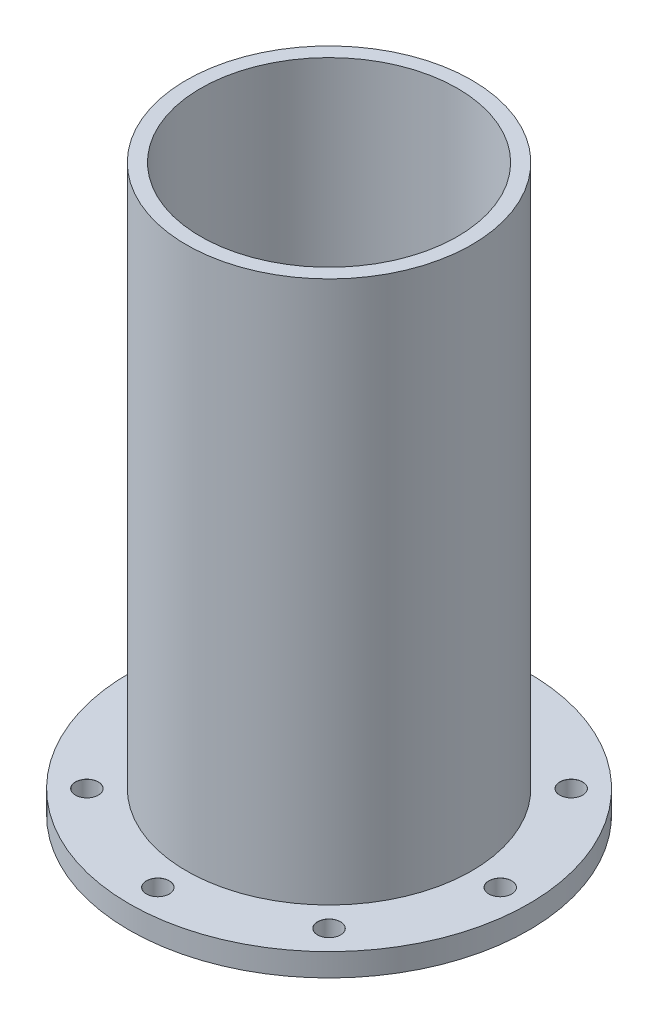
SolidWorks part; units mm, degrees
ref_plane "Front Plane" through (0, 0, 0) normal (0, 0, 1) x (1, 0, 0)
ref_plane "Top Plane" through (0, 0, 0) normal (0, 1, 0) x (1, 0, 0)
ref_plane "Right Plane" through (0, 0, 0) normal (1, 0, 0) x (0, 0, -1)
sketch "草图1" plane through (0, 0, 0) normal (0, 0, 1) x (1, 0, 0)
  line L0 (0, 76.6195) -> (0, -49.9786) construction
  line L13 (0, 0) -> (-70, 0)
  line L14 (0, 0) -> (0, 8)
  line L15 (0, 8) -> (-70, 8)
  line L16 (-70, 0) -> (-70, 8)
  dimension "D1" = 70
  dimension "D2" = 8
revolve "旋转1" add sketch "草图1" angle 360 about L0
sketch "草图8" plane through (0, 8, 0) normal (0, 1, 0) x (1, 0, 0)
  circle A0 centre (0, 0) radius 60
  dimension "D1" = 120
hole_wizard "M8x1.0 螺纹孔2" positions "草图9" profile "草图10" tap size "M8x1.0" standard "GB" end condition through all
sketch "草图9" plane through (0, 8, 0) normal (0, 1, 0) x (1, 0, 0)
  circle A0 centre (0, 0) radius 60 construction
  point P0 (-60, 0)
sketch "草图10" plane through (-60, 8, 0) normal (1, 0, 0) x (0, 0, 1)
  line L0 (0, 0) -> (0, 8)
  line L1 (0, 8) -> (4, 8)
  line L2 (4, 8) -> (4, 0.021)
  line L3 (4, 0.021) -> (4.025, 0)
  line L5 (4.025, 0) -> (0, 0)
  line L6 (-4, 0.021) -> (-4.025, 0) construction
  line L11 (0, -6.35) -> (0, 107.95) construction
  dimension "通孔螺纹孔钻头直径" = 8
  dimension "通孔螺纹孔钻头深度" = 8
  dimension "近端锥形沉头孔直径" = 8.05
  dimension "近端锥形沉头孔角度" = 100
cosmetic thread "孔螺蚊线9" parameters "D2"=8
pattern_circular "阵列(圆周)2" count 8 over 360 about axis through (0, 76.6195, 0) along (0, -1, 0) of "M8x1.0 螺纹孔2"
cosmetic thread "孔螺蚊线10" parameters "D2"=8
cosmetic thread "孔螺蚊线11" parameters "D2"=8
cosmetic thread "孔螺蚊线12" parameters "D2"=8
cosmetic thread "孔螺蚊线13" parameters "D2"=8
cosmetic thread "孔螺蚊线14" parameters "D2"=8
cosmetic thread "孔螺蚊线15" parameters "D2"=8
cosmetic thread "孔螺蚊线16" parameters "D2"=8
sketch "草图11" plane through (0, 0, 0) normal (0, 0, 1) x (1, 0, 0)
  line L1 (0, 8) -> (-50, 8)
  line L2 (0, 8) -> (0, 198)
  line L3 (0, 198) -> (-50, 198)
  line L4 (-50, 8) -> (-50, 198)
  dimension "D1" = 50
  dimension "D2" = 190
revolve "旋转2" add sketch "草图11" angle 360 about L2
sketch "草图12" plane through (0, 0, 0) normal (0, -1, 0) x (1, 0, 0)
  circle A0 centre (0, 0) radius 45
  dimension "D1" = 90
extrude "切除-拉伸1" cut sketch "草图12" against normal through all
ref_axis "基准轴1" through (0, 10, 0) along (0, 1, 0)
